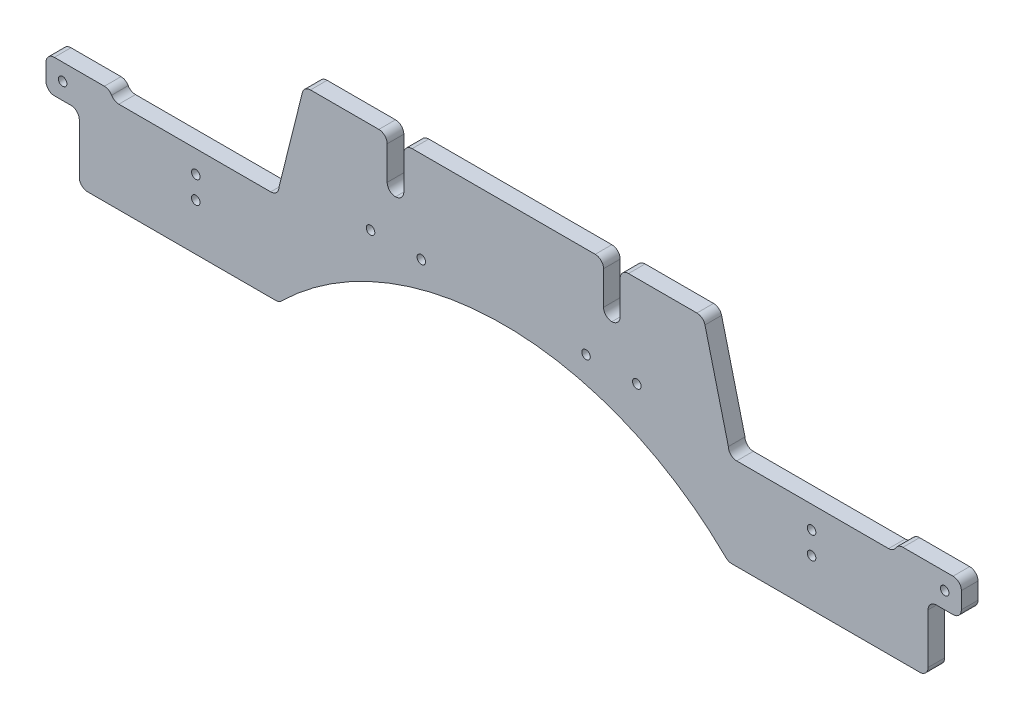
SolidWorks part; units mm, degrees
material "6061 Alloy"
ref_plane "Front Plane" through (0, 0, 0) normal (0, 0, 1) x (1, 0, 0)
ref_plane "Top Plane" through (0, 0, 0) normal (0, 1, 0) x (1, 0, 0)
ref_plane "Right Plane" through (0, 0, 0) normal (1, 0, 0) x (0, 0, -1)
sketch "Sketch1" plane through (0, 0, 0) normal (0, 0, 1) x (1, 0, 0)
  line L0 (-323.85, -18.4471) -> (-171.45, -18.4471)
  line L1 (-349.25, 32.3529) -> (-349.25, 57.7529)
  line L2 (-349.25, 57.7529) -> (-300.0375, 57.7529)
  line L3 (-300.0375, 57.7529) -> (-300.0375, 51.4029)
  line L4 (-300.0375, 51.4029) -> (-171.45, 51.4029)
  line L5 (171.45, 51.4029) -> (300.0375, 51.4029)
  line L9 (-88.9, 133.9529) -> (-88.9, 95.7767)
  line L10 (-88.9, 95.7767) -> (-76.2, 95.7767)
  line L11 (-76.2, 133.9529) -> (-76.2, 95.7767)
  line L15 (-76.2, 133.9529) -> (76.2, 133.9529)
  line L16 (-349.25, 32.3529) -> (-323.85, 32.3529)
  line L19 (-323.85, 32.3529) -> (-323.85, -18.4471)
  line L22 (0, 223.7282) -> (0, -57.3148) construction
  line L23 (-171.45, 51.4029) -> (-171.45, 57.7529)
  line L25 (-152.4, 133.9529) -> (-88.9, 133.9529)
  line L26 (-171.45, 57.7529) -> (-152.4, 133.9529)
  line L27 (171.45, 57.7529) -> (152.4, 133.9529)
  line L28 (152.4, 133.9529) -> (88.9, 133.9529)
  line L30 (171.45, 51.4029) -> (171.45, 57.7529)
  line L33 (323.85, 32.3529) -> (323.85, -18.4471)
  line L36 (349.25, 32.3529) -> (323.85, 32.3529)
  line L40 (76.2, 133.9529) -> (76.2, 95.7767)
  line L41 (88.9, 95.7767) -> (76.2, 95.7767)
  line L42 (88.9, 133.9529) -> (88.9, 95.7767)
  line L48 (300.0375, 57.7529) -> (300.0375, 51.4029)
  line L49 (349.25, 57.7529) -> (300.0375, 57.7529)
  line L50 (349.25, 32.3529) -> (349.25, 57.7529)
  line L51 (323.85, -18.4471) -> (171.45, -18.4471)
  circle A0 centre (-234.95, 178.4029) radius 76.2 construction
  arc A1 (-171.45, -18.4471) -> (171.45, -18.4471) centre (0, -189.8971) cw
  circle A2 centre (-336.55, 45.0529) radius 3.2639
  circle A3 centre (336.55, 45.0529) radius 3.2639
  point P4 (0, 0)
  point P34 (0, 133.9529)
  dimension "D3" = 152.4
  dimension "D11" = 260.35
  dimension "D10" = 49.2125
  dimension "D4" = 6.5278
  dimension "D8" = 12.7
  dimension "D13" = 12.7
  dimension "D2" = 25.4
  dimension "D5" = 38.1762
  dimension "D6" = 12.7
  dimension "D7" = 76.2
  dimension "D9" = 63.5
  dimension "D12" = 50.8
  dimension "D14" = 25.4
  dimension "D17" = 152.4
extrude "Boss-Extrude1" add sketch "Sketch1" along normal mid plane 12.7
fillet "Fillet1" radius 6.35 10 edges at (88.9, 95.7767, 0) (76.2, 95.7767, 0) (-88.9, 95.7767, 0) (-76.2, 95.7767, 0) (323.85, 32.3529, 0) (171.45, 51.4029, 0) (300.0375, 51.4029, 0) (-171.45, 51.4029, 0) (-300.0375, 51.4029, 0) (-323.85, 32.3529, 0)
sketch "Sketch2" plane through (0, 0, 6.35) normal (0, 0, 1) x (1, 0, 0)
  line L0 (-177.8, 51.4029) -> (-293.6875, 51.4029) construction
  line L1 (-244.475, 51.4029) -> (-234.95, 51.4029)
  line L2 (-244.475, 51.4029) -> (-244.475, 13.3029)
  line L3 (-244.475, 13.3029) -> (-225.425, 13.3029)
  line L4 (-225.425, 51.4029) -> (-225.425, 13.3029)
  line L5 (-234.95, 51.4029) -> (-234.95, 34.3849) construction
  line L6 (-234.95, 51.4029) -> (-225.425, 51.4029)
  line L7 (-234.95, 34.3849) -> (-234.95, 17.3669) construction
  line L8 (-234.95, 17.3669) -> (-234.95, 13.3029) construction
  line L9 (0, 168.5341) -> (0, -83.3035) construction
  line L10 (234.95, 17.3669) -> (234.95, 13.3029) construction
  line L11 (234.95, 34.3849) -> (234.95, 17.3669) construction
  line L12 (234.95, 51.4029) -> (234.95, 34.3849) construction
  line L13 (234.95, 51.4029) -> (225.425, 51.4029)
  line L14 (225.425, 51.4029) -> (225.425, 13.3029)
  line L15 (244.475, 13.3029) -> (225.425, 13.3029)
  line L16 (244.475, 51.4029) -> (244.475, 13.3029)
  line L17 (244.475, 51.4029) -> (234.95, 51.4029)
  circle A0 centre (-234.95, 34.3849) radius 3.2639
  circle A1 centre (-234.95, 17.3669) radius 3.2639
  circle A2 centre (234.95, 17.3669) radius 3.2639
  circle A3 centre (234.95, 34.3849) radius 3.2639
  dimension "D3" = 6.5278
  dimension "D1" = 38.1
  dimension "D2" = 19.05
  dimension "D4" = 17.018
  dimension "D5" = 17.018
extrude "Cut-Extrude2" cut sketch "Sketch2" against normal through all contours A1 | A0 | A3 | A2 region at (-234.95, 34.3849, 6.35) region at (-234.95, 17.3669, 6.35) region at (234.95, 17.3669, 6.35) region at (234.95, 34.3849, 6.35)
sketch "Sketch3" plane through (0, 0, 6.35) normal (0, 0, 1) x (1, 0, 0)
  line L0 (-114.3, 64.1986) -> (-101.6, 64.1986) construction
  line L1 (-88.9, 57.8486) -> (-114.3, 57.8486)
  line L2 (-88.9, 57.8486) -> (-88.9, 70.5486)
  line L3 (-88.9, 70.5486) -> (-114.3, 70.5486)
  line L4 (-114.3, 57.8486) -> (-114.3, 70.5486)
  line L5 (-101.6, 64.1986) -> (-88.9, 64.1986) construction
  line L6 (0, -27.884) -> (0, 144.8765) construction
  line L7 (101.6, 64.1986) -> (88.9, 64.1986) construction
  line L8 (114.3, 64.1986) -> (101.6, 64.1986) construction
  line L9 (114.3, 57.8486) -> (114.3, 70.5486)
  line L10 (88.9, 70.5486) -> (114.3, 70.5486)
  line L11 (88.9, 57.8486) -> (88.9, 70.5486)
  line L12 (88.9, 57.8486) -> (114.3, 57.8486)
  line L13 (-62.8345, 64.1986) -> (-76.2, 64.1986) construction
  line L14 (-76.2, 70.5486) -> (-50.8, 70.5486)
  line L15 (-76.2, 70.5486) -> (-76.2, 57.8486)
  line L16 (-76.2, 57.8486) -> (-50.8, 57.8486)
  line L17 (-50.8, 70.5486) -> (-50.8, 57.8486)
  line L18 (50.8, 64.1986) -> (62.8345, 64.1986) construction
  line L19 (-50.8, 64.1986) -> (-62.8345, 64.1986) construction
  line L20 (62.8345, 64.1986) -> (76.2, 64.1986) construction
  line L21 (50.8, 70.5486) -> (50.8, 57.8486)
  line L22 (76.2, 57.8486) -> (50.8, 57.8486)
  line L23 (76.2, 70.5486) -> (76.2, 57.8486)
  line L24 (76.2, 70.5486) -> (50.8, 70.5486)
  line L25 (-82.55, 95.7767) -> (-82.55, 38.0847) construction
  line L26 (82.55, 95.7767) -> (82.55, 38.0847) construction
  circle A0 centre (-101.6, 64.1986) radius 3.2639
  circle A1 centre (101.6, 64.1986) radius 3.2639
  circle A2 centre (-62.8345, 64.1986) radius 3.2639
  circle A3 centre (62.8345, 64.1986) radius 3.2639
  arc A4 (171.45, -18.4471) -> (-171.45, -18.4471) centre (0, -189.8971) ccw construction
  dimension "D3" = 6.5278
  dimension "D1" = 12.7
  dimension "D2" = 25.4
  dimension "D4" = 25.4
  dimension "D5" = 12.7
extrude "Cut-Extrude3" cut sketch "Sketch3" against normal through all contours A0 | A1 | A2 | A3 region at (-101.6, 64.1986, 6.35) region at (101.6, 64.1986, 6.35) region at (-62.8345, 64.1986, 6.35)
fillet "Fillet2" radius 6.35 16 edges at (-88.9, 133.9529, 0) (-76.2, 133.9529, 0) (76.2, 133.9529, 0) (88.9, 133.9529, 0) (152.4, 133.9529, 0) (-152.4, 133.9529, 0) (349.25, 57.7529, 0) (349.25, 32.3529, 0) (323.85, -18.4471, 0) (171.45, -18.4471, 0) (-171.45, -18.4471, 0) (-323.85, -18.4471, 0) (-349.25, 32.3529, 0) (-349.25, 57.7529, 0) (-300.0375, 57.7529, 0) (300.0375, 57.7529, 0)
